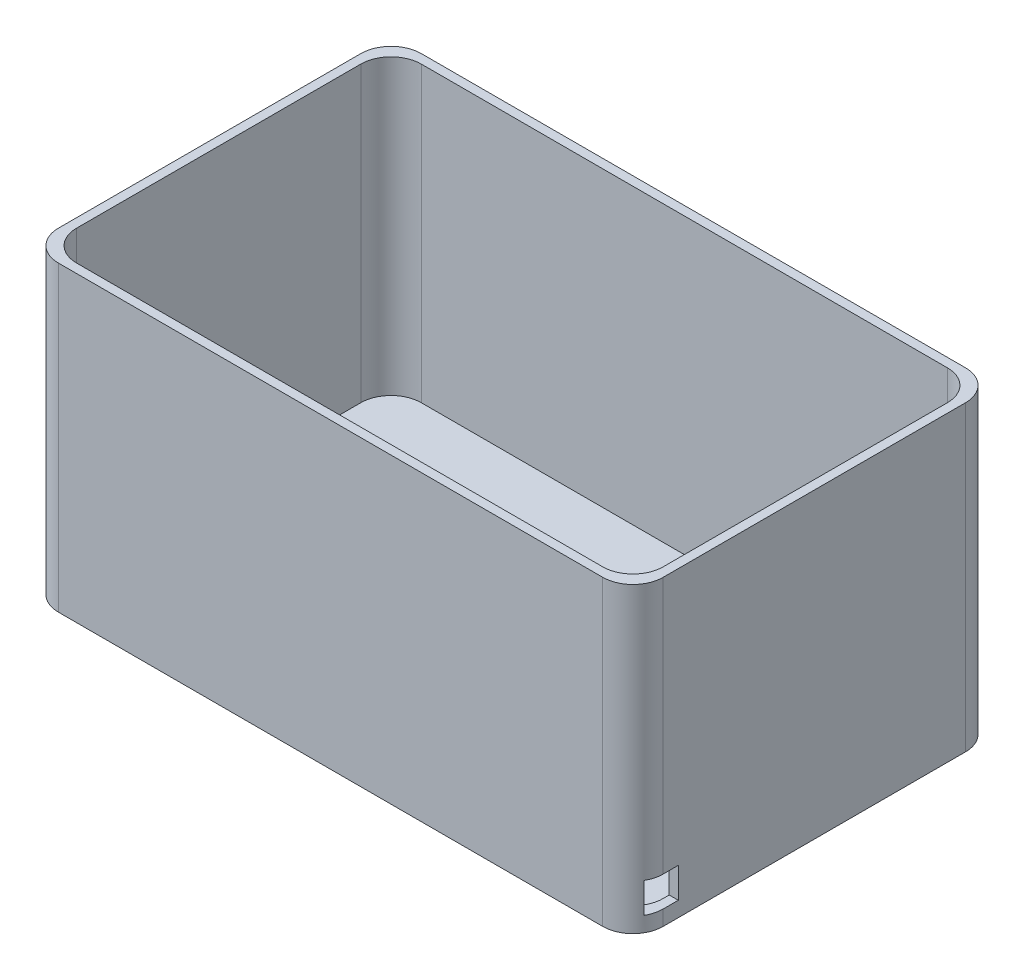
SolidWorks part; units mm, degrees
ref_plane "Front Plane" through (0, 0, 0) normal (0, 0, 1) x (1, 0, 0)
ref_plane "Top Plane" through (0, 0, 0) normal (0, 1, 0) x (1, 0, 0)
ref_plane "Right Plane" through (0, 0, 0) normal (1, 0, 0) x (0, 0, -1)
sketch "Sketch1" plane through (0, 0, 0) normal (0, 1, 0) x (1, 0, 0)
  line L0 (-100, -60) -> (100, 60) construction
  line L1 (-100, 60) -> (100, 60)
  line L2 (-100, 60) -> (-100, -60)
  line L3 (-100, -60) -> (100, -60)
  line L4 (100, 60) -> (100, -60)
  point P4 (0, 0)
  dimension "D1" = 120
  dimension "D2" = 200
extrude "Boss-Extrude1" add sketch "Sketch1" along normal blind 100 contours L3 L4 L1 L2
shell "Shell1" thickness 3 removed face at (0, 100, 0)
sketch "Sketch5" plane through (100, 0, 0) normal (1, 0, 0) x (0, 0, -1)
  line L0 (60, 0) -> (-60, 0) construction
  line L1 (-55, 15) -> (-45, 15)
  line L2 (-55, 15) -> (-55, 5)
  line L3 (-55, 5) -> (-45, 5)
  line L4 (-45, 15) -> (-45, 5)
  line L5 (-60, 100) -> (-60, 0) construction
  dimension "D1" = 5
  dimension "D2" = 5
  dimension "D3" = 10
  dimension "D4" = 10
extrude "Cut-Extrude1" cut sketch "Sketch5" against normal up to next and the other way through all
fillet "Fillet2" radius 10 4 edges at (-100, 50, -60) (-100, 50, 60) (100, 50, 60) (100, 50, -60)
fillet "Fillet3" radius 10 4 edges at (-97, 51.5, 57) (97, 51.5, 57) (-97, 51.5, -57) (97, 51.5, -57)
